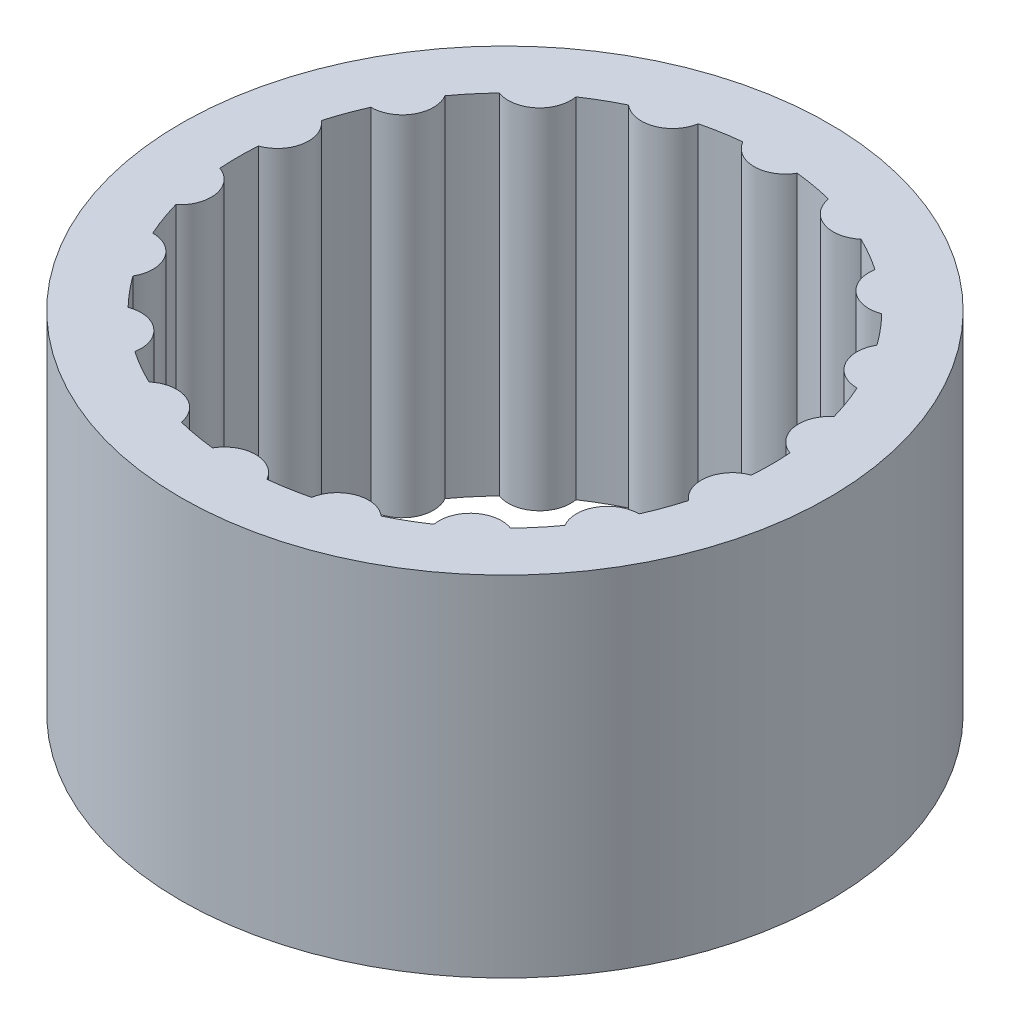
SolidWorks part; units mm, degrees
material "AISI 1020"
ref_plane "Front Plane" through (0, 0, 0) normal (0, 0, 1) x (1, 0, 0)
ref_plane "Top Plane" through (0, 0, 0) normal (0, 1, 0) x (1, 0, 0)
ref_plane "Right Plane" through (0, 0, 0) normal (1, 0, 0) x (0, 0, -1)
sketch "Sketch1" plane through (0, 0, 0) normal (0, 1, 0) x (1, 0, 0)
  circle A0 centre (0, 0) radius 7.9375
  circle A1 centre (0, 0) radius 10.3187
  dimension "D1" = 15.875
  dimension "D2" = 20.6375
extrude "Boss-Extrude1" add sketch "Sketch1" along normal blind 11.1125
sketch "Sketch2" plane through (0, 11.1125, 0) normal (0, 1, 0) x (1, 0, 0)
  circle A0 centre (0, 0) radius 7.9375
  circle A1 centre (0, 0) radius 8.4861
  arc A4 (-0.865, 8.4419) -> (0.865, 8.4419) centre (0, 8.9314) ccw
  arc A5 (2.0745, 8.2286) -> (3.7001, 7.6369) centre (3.0547, 8.3928) ccw
  arc A6 (4.7637, 7.0228) -> (6.0889, 5.9108) centre (5.741, 6.8419) ccw
  arc A7 (6.8784, 4.97) -> (7.7434, 3.4718) centre (7.7348, 4.4657) ccw
  arc A8 (8.1634, 2.3178) -> (8.4638, 0.6141) centre (8.7957, 1.5509) ccw
  arc A9 (8.4638, -0.6141) -> (8.1634, -2.3178) centre (8.7957, -1.5509) ccw
  arc A10 (7.7434, -3.4718) -> (6.8784, -4.97) centre (7.7348, -4.4657) ccw
  arc A11 (6.0889, -5.9108) -> (4.7637, -7.0228) centre (5.741, -6.8419) ccw
  arc A12 (3.7001, -7.6369) -> (2.0745, -8.2286) centre (3.0547, -8.3928) ccw
  arc A13 (0.865, -8.4419) -> (-0.865, -8.4419) centre (0, -8.9314) ccw
  arc A14 (-2.0745, -8.2286) -> (-3.7001, -7.6369) centre (-3.0547, -8.3928) ccw
  arc A15 (-4.7637, -7.0228) -> (-6.0889, -5.9108) centre (-5.741, -6.8419) ccw
  arc A16 (-6.8784, -4.97) -> (-7.7434, -3.4718) centre (-7.7348, -4.4657) ccw
  arc A17 (-8.1634, -2.3178) -> (-8.4638, -0.6141) centre (-8.7957, -1.5509) ccw
  arc A18 (-8.4638, 0.6141) -> (-8.1634, 2.3178) centre (-8.7957, 1.5509) ccw
  arc A19 (-7.7434, 3.4718) -> (-6.8784, 4.97) centre (-7.7348, 4.4657) ccw
  arc A20 (-6.0889, 5.9108) -> (-4.7637, 7.0228) centre (-5.741, 6.8419) ccw
  arc A21 (-3.7001, 7.6369) -> (-2.0745, 8.2286) centre (-3.0547, 8.3928) ccw
  point P7 (0, 8.4094)
  point P8 (0, 8.4094)
  point P12 (0, 8.4419)
  point P63 (0, 0)
  circle M27 centre (0, 0) radius 7.9375
  dimension "D1" = 18
extrude "Cut-Extrude1" cut sketch "Sketch2" against normal blind 11.1125 contours A5 A1 A4 M27 | A21 A0 A4 A1 | A21 A1 A20 M27 | A20 A1 A19 A0 | A19 A1 A18 M27 | A18 A1 A17 A0 | A17 A1 A16 M27 | A16 A1 A15 A0 | A15 A1 A14 M27 | A14 A1 A13 A0 | A13 A1 A12 M27 | A12 A1 A11 A0 | A11 A1 A10 M27 | A10 A1 A9 A0 | A7 A1 A6 M27 | A6 A1 A5 A0 | A8 A1 A7 A0 | A9 A1 A8 M27 region at (8.1641, 11.1125, 0) region at (7.6718, 11.1125, -2.7923) region at (7.6718, 11.1125, 2.7923) region at (6.2541, 11.1125, -5.2478) region at (6.2541, 11.1125, 5.2478) region at (4.0821, 11.1125, -7.0703) region at (4.0821, 11.1125, 7.0703) region at (1.4177, 11.1125, -8.0401) region at (1.4177, 11.1125, 8.0401) region at (-1.4177, 11.1125, -8.0401) region at (-1.4177, 11.1125, 8.0401) region at (-4.0821, 11.1125, -7.0703) region at (-4.0821, 11.1125, 7.0703) region at (-6.2541, 11.1125, -5.2478) region at (-6.2541, 11.1125, 5.2478) region at (-7.6718, 11.1125, -2.7923) region at (-7.6718, 11.1125, 2.7923) region at (-8.1641, 11.1125, 0)
